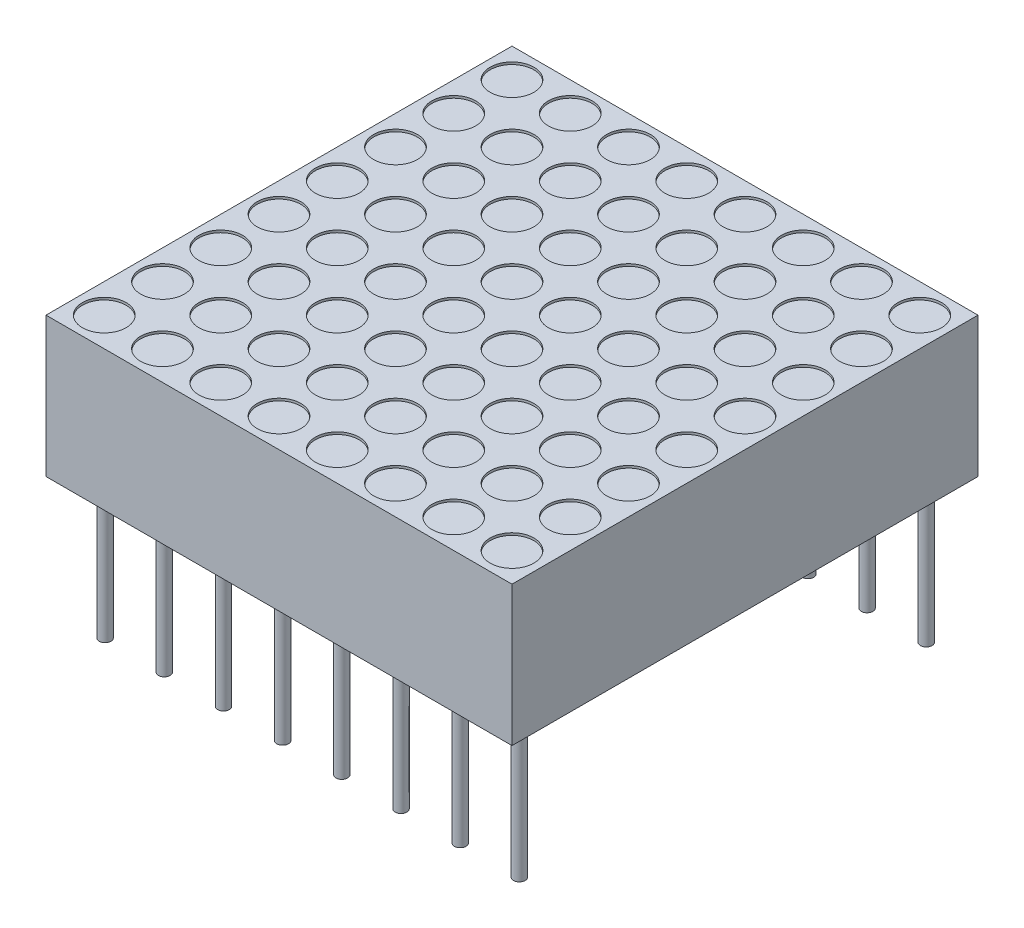
SolidWorks part; units mm, degrees
ref_plane "Alzado" through (0, 0, 0) normal (0, 0, 1) x (1, 0, 0)
ref_plane "Planta" through (0, 0, 0) normal (0, 1, 0) x (1, 0, 0)
ref_plane "Vista lateral" through (0, 0, 0) normal (1, 0, 0) x (0, 0, -1)
sketch "Croquis1" plane through (0, 0, 0) normal (0, 1, 0) x (1, 0, 0)
  line L1 (-10, 10) -> (10, 10)
  line L2 (-10, 10) -> (-10, -10)
  line L3 (-10, -10) -> (10, -10)
  line L4 (10, 10) -> (10, -10)
  line L5 (-10, 10) -> (10, -10) construction
  line L6 (-10, -10) -> (10, 10) construction
  point P0 (0, 0)
  dimension "D1" = 20
  dimension "D2" = 20
extrude "Saliente-Extruir1" add sketch "Croquis1" along normal blind 3 and the other way blind 3
sketch "Croquis2" plane through (0, 3, 0) normal (0, 1, 0) x (1, 0, 0)
  line L0 (-10, 10) -> (-10, -10) construction
  line L1 (10, 10) -> (-10, 10) construction
  circle A0 centre (-8.75, 8.75) radius 0.9375
  dimension "D1" = 1.875
  dimension "D2" = 1.25
  dimension "D3" = 1.25
extrude "Cortar-Extruir4" cut sketch "Croquis2" against normal blind 0.1
pattern_linear "MatrizL1" count 8 spacing 2.5 along (1, 0, 0) count 8 spacing 2.5 along (0, 0, 1) of "Cortar-Extruir4"
sketch "Croquis3" plane through (0, 0, 10) normal (0, 0, 1) x (1, 0, 0)
  line L0 (-6.1945, 1.4779) -> (-4.4336, 1.4779) construction
  line L1 (-4.4336, 1.4779) -> (-5.314, -0.7547) construction
  line L2 (1.8552, 1.4779) -> (1.8552, -1.1815) construction
  line L3 (10, -3) -> (10, 3) construction
  line L4 (-10, 3) -> (10, 3) construction
  circle A0 centre (-2.9235, 0.8823) radius 0.6059 construction
  circle A1 centre (-2.9235, -0.4075) radius 0.7853 construction
  circle A2 centre (-0.4402, 0.8823) radius 0.6657 construction
  circle A3 centre (-0.4402, -0.4075) radius 0.774 construction
  arc A4 (1.8552, 1.4779) -> (2.9557, 0) centre (2.4055, 0.7389) cw construction
  arc A5 (2.9557, 0) -> (1.8552, -1.1815) centre (2.4055, -0.5908) cw construction
  spline S0 degree 3 poles (5.7543, 1.4779) (1.4927, 1.585) (8.8589, -0.2655) (4.5279, -1.141) knots 0 0 0 0 1 1 1 1 construction
  dimension "D1" = 1.548
  dimension "D2" = 1.5707
  dimension "D3" = 1.2118
  dimension "D4" = 1.3313
  dimension "D5" = 0.9213
  dimension "D6" = 0.8073
  dimension "D7" = 4.2143
  dimension "D8" = 4.2457
  dimension "D9" = 5.4721
  dimension "D10" = 5.5978
  dimension "D11" = 7.5945
  dimension "D12" = 8.1448
  dimension "D13" = 10.4402
  dimension "D14" = 12.9235
  dimension "D15" = 1.5221
  dimension "D16" = 1.8366
  dimension "D17" = 2.1177
  dimension "D18" = 3
  dimension "D19" = 0.8804
  dimension "D20" = 3.4075
  dimension "D21" = 1.7609
  dimension "D22" = 4.141
  dimension "D23" = 5.314
  dimension "D24" = 3.2465
sketch "Croquis4" plane through (0, -3, 0) normal (0, -1, 0) x (-1, 0, 0)
  line L0 (10, 10) -> (10, -10) construction
  line L1 (10, -10) -> (-10, -10) construction
  circle A0 centre (8.7312, -8.7312) radius 0.25
  dimension "D1" = 0.5
  dimension "D2" = 1.2688
  dimension "D3" = 1.2688
extrude "Saliente-Extruir2" add sketch "Croquis4" along normal blind 6
pattern_linear "MatrizL2" count 8 spacing 2.54 along (1, 0, 0) count 2 spacing 17.4625 along (0, 0, -1) of "Saliente-Extruir2"
